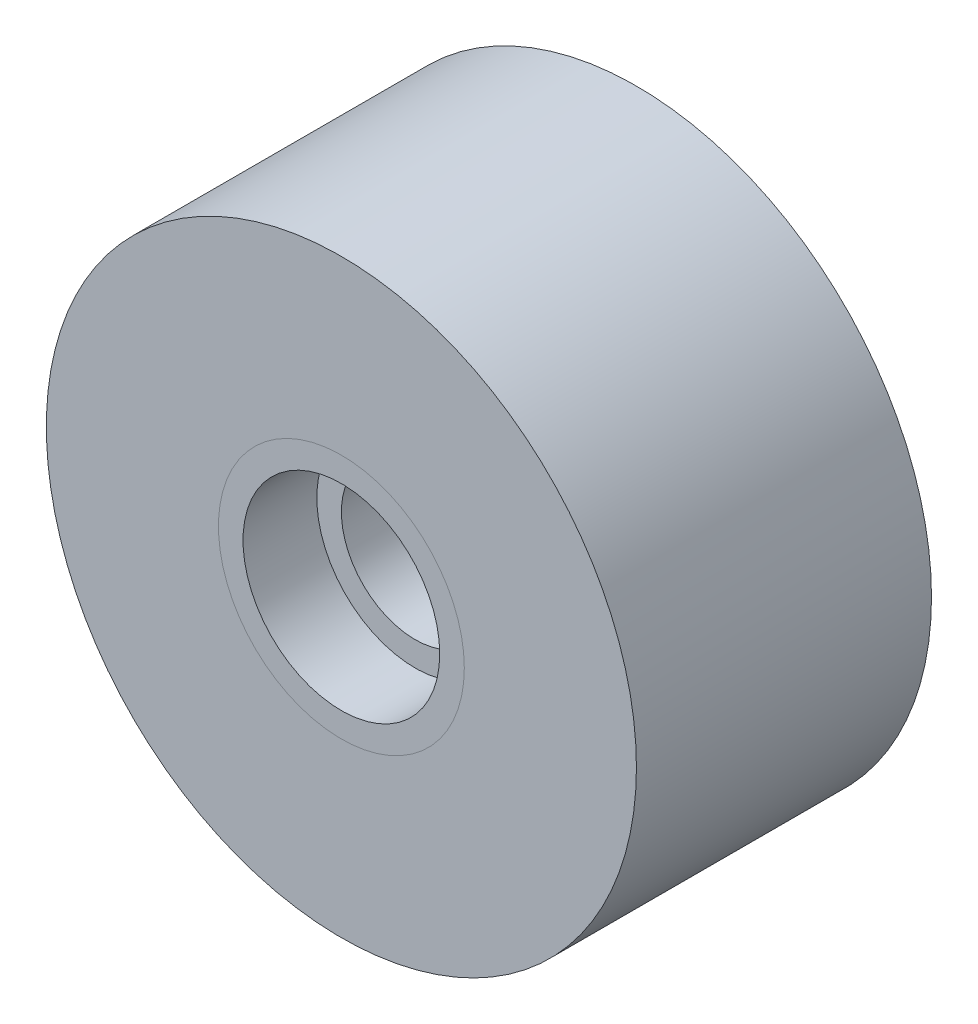
SolidWorks part; units mm, degrees
ref_plane "前视基准面" through (0, 0, 0) normal (0, 0, 1) x (1, 0, 0)
ref_plane "上视基准面" through (0, 0, 0) normal (0, 1, 0) x (1, 0, 0)
ref_plane "右视基准面" through (0, 0, 0) normal (1, 0, 0) x (0, 0, -1)
sketch "草图1" plane through (0, 0, 0) normal (0, 0, 1) x (1, 0, 0)
  circle A0 centre (0, 0) radius 12
  circle A1 centre (0, 0) radius 5
  circle A2 centre (0, 0) radius 3
  circle A3 centre (0, 0) radius 4
  dimension "D1" = 24
  dimension "D2" = 10
  dimension "D3" = 6
  dimension "D4" = 8
extrude "凸台-拉伸1" add sketch "草图1" along normal mid plane 12 contours A0 A1 region at (-11.6606, 0, 0)
extrude "凸台-拉伸2" add sketch "草图1<3>" along normal mid plane 12 separate body contours A1 A2 region at (-4.8586, 0, 0)
sketch "草图1<3>" plane through (0, 0, 0) normal (0, 0, 1) x (1, 0, 0) same geometry as "草图1"
extrude "凸台-拉伸3" add sketch "草图1<4>" along normal mid plane 6 contours A3 A2 region at (-3.8869, 0, 0)
sketch "草图1<4>" plane through (0, 0, 0) normal (0, 0, 1) x (1, 0, 0) same geometry as "草图1"
